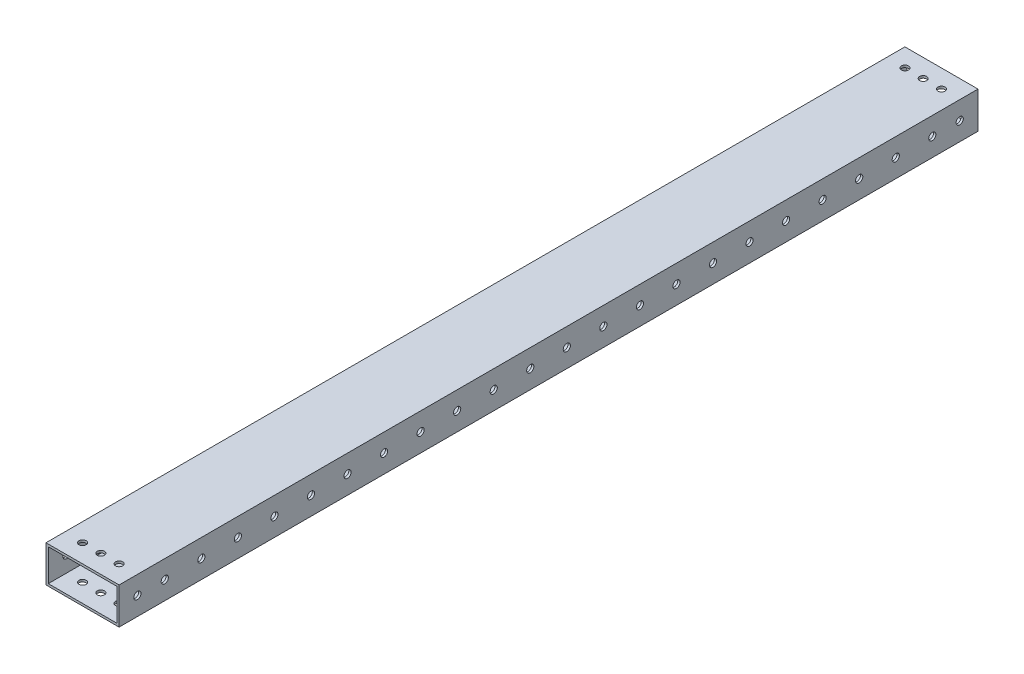
SolidWorks part; units mm, degrees
material "6061-T6 (SS)"
ref_plane "Front Plane" through (0, 0, 0) normal (0, 0, 1) x (1, 0, 0)
ref_plane "Top Plane" through (0, 0, 0) normal (0, 1, 0) x (1, 0, 0)
ref_plane "Right Plane" through (0, 0, 0) normal (1, 0, 0) x (0, 0, -1)
sketch "Sketch1" plane through (0, 0, 0) normal (0, 0, 1) x (1, 0, 0)
  line L1 (0, 0) -> (50.8, 0)
  line L2 (0, 0) -> (0, 25.4)
  line L3 (0, 25.4) -> (50.8, 25.4)
  line L4 (50.8, 0) -> (50.8, 25.4)
  dimension "D1" = 50.8
  dimension "D2" = 25.4
extrude "Boss-Extrude1" add sketch "Sketch1" along normal mid plane 596.9
shell "Shell1" thickness 1.5875 removed face at (25.4, 12.7, -298.45) removed face at (25.4, 12.7, 298.45)
sketch "Sketch2" plane through (0, 25.4, 0) normal (0, 1, 0) x (1, 0, 0)
  line L0 (50.8, -298.45) -> (50.8, 298.45) construction
  line L1 (50.8, -298.45) -> (0, -298.45) construction
  circle A0 centre (38.1, -285.75) radius 2.4892
  circle A1 centre (25.4, -285.75) radius 2.4892
  circle A2 centre (12.7, -285.75) radius 2.4892
  dimension "D1" = 4.9784
  dimension "D2" = 12.7
  dimension "D3" = 12.7
  dimension "D4" = 12.7
  dimension "D5" = 12.7
extrude "Cut-Extrude1" cut sketch "Sketch2" against normal through all
sketch "Sketch3" plane through (50.8, 0, 0) normal (1, 0, 0) x (0, 0, -1)
  line L0 (-298.45, 25.4) -> (298.45, 25.4) construction
  line L1 (-298.45, 0) -> (-298.45, 25.4) construction
  circle A0 centre (-285.75, 12.7) radius 2.4892
  dimension "D1" = 4.9784
  dimension "D2" = 12.7
  dimension "D3" = 12.7
extrude "Cut-Extrude2" cut sketch "Sketch3" against normal through all
mirror "Mirror1" about plane through (0, 0, 0) normal (0, 0, 1) of "Cut-Extrude1", "Cut-Extrude2"
sketch "Sketch4" plane through (50.8, 0, 0) normal (1, 0, 0) x (0, 0, -1)
  line L0 (-285.75, 12.7) -> (-266.7, 12.7) construction
  line L1 (-298.45, 0) -> (298.45, 0) construction
  line L2 (-298.45, 0) -> (-298.45, 25.4) construction
  circle A0 centre (-266.7, 12.7) radius 2.4892
  dimension "D1" = 4.9784
  dimension "D2" = 31.75
extrude "Cut-Extrude3" cut sketch "Sketch4" against normal through all and the other way through all
pattern_linear "LPattern1" count 22 spacing 25.4 along (0, 0, -1) of "Cut-Extrude3"
